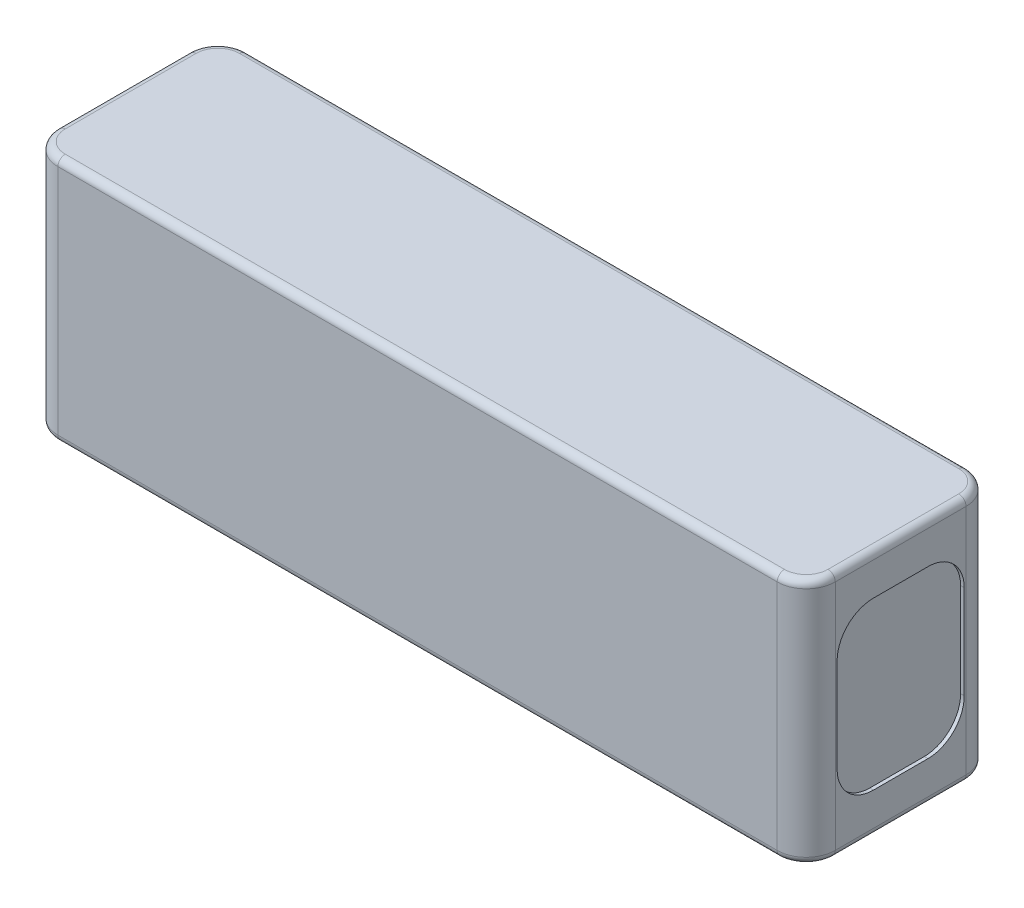
SolidWorks part; units mm, degrees
ref_plane "Front Plane" through (0, 0, 0) normal (0, 0, 1) x (1, 0, 0)
ref_plane "Top Plane" through (0, 0, 0) normal (0, 1, 0) x (1, 0, 0)
ref_plane "Right Plane" through (0, 0, 0) normal (1, 0, 0) x (0, 0, -1)
ref_plane "Plane1" through (0, 0, -15) normal (0, 0, -1) x (-1, 0, 0)
sketch "Sketch1" plane through (0, 0, -15) normal (0, 0, -1) x (-1, 0, 0)
  line L0 (-69, -22) -> (38, -22)
  line L1 (38, -22) -> (38, 12)
  line L2 (38, 12) -> (-69, 12)
  line L3 (-69, 12) -> (-69, -22)
  line L4 (-69, -5) -> (38, -5) construction
  line L5 (-15.5, 12) -> (-15.5, -22) construction
  dimension "D1" = 34
  dimension "D2" = 107
extrude "Boss-Extrude1" add sketch "Sketch1" against normal blind 26
sketch "Sketch2" plane through (69, 0, 0) normal (1, 0, 0) x (0, 0, -1)
  line L0 (-6.75, 1.4423) -> (-6.75, -11.4423)
  line L1 (-1.75, -16.4423) -> (5.75, -16.4423)
  line L2 (10.75, -11.4423) -> (10.75, 1.4423)
  line L3 (5.75, 6.4423) -> (-1.75, 6.4423)
  line L4 (-11, 12) -> (15, -22) construction
  line L5 (15, 12) -> (-11, -22) construction
  line L6 (-6.75, 6.4423) -> (10.75, -16.4423) construction
  line L7 (10.75, 6.4423) -> (-6.75, -16.4423) construction
  line L12 (-11, 12) -> (15, 12) construction
  line L13 (-11, 12) -> (-11, -22) construction
  line L14 (-11, -22) -> (15, -22) construction
  line L15 (15, 12) -> (15, -22) construction
  line L16 (-11, 12) -> (15, -22) construction
  line L17 (-11, -22) -> (15, 12) construction
  arc A0 (-6.75, -11.4423) -> (-1.75, -16.4423) centre (-1.75, -11.4423) ccw
  arc A1 (5.75, -16.4423) -> (10.75, -11.4423) centre (5.75, -11.4423) ccw
  arc A2 (10.75, 1.4423) -> (5.75, 6.4423) centre (5.75, 1.4423) ccw
  arc A3 (-6.75, 1.4423) -> (-1.75, 6.4423) centre (-1.75, 1.4423) cw
  point P16 (2, -5)
  dimension "D2" = 26
  dimension "D3" = 5
  dimension "D1" = 17.5
extrude "Cut-Extrude1" cut sketch "Sketch2" against normal blind 0.5
sketch "Sketch3" plane through (-38, 0, 0) normal (-1, 0, 0) x (0, 0, 1)
  line L0 (-0.625, 7.2596) -> (-3.375, 7.2596)
  line L1 (-11.375, -0.7404) -> (-11.375, -9.2596)
  line L2 (-3.375, -17.2596) -> (-0.625, -17.2596)
  line L3 (7.375, -9.2596) -> (7.375, -0.7404)
  line L4 (-11.375, 7.2596) -> (7.375, -17.2596) construction
  line L5 (7.375, 7.2596) -> (-11.375, -17.2596) construction
  line L6 (-15, 12) -> (11, -22) construction
  line L7 (11, -22) -> (-15, -22) construction
  line L8 (-15, -22) -> (11, 12) construction
  arc A0 (-11.375, -9.2596) -> (-3.375, -17.2596) centre (-3.375, -9.2596) ccw
  arc A1 (-0.625, -17.2596) -> (7.375, -9.2596) centre (-0.625, -9.2596) ccw
  arc A2 (-0.625, 7.2596) -> (7.375, -0.7404) centre (-0.625, -0.7404) cw
  arc A3 (-3.375, 7.2596) -> (-11.375, -0.7404) centre (-3.375, -0.7404) ccw
  dimension "D3" = 8
  dimension "D1" = 18.75
  dimension "D2" = 26
extrude "Cut-Extrude2" cut sketch "Sketch3" against normal blind 0.5
fillet "Fillet1" radius 4 4 edges at (-38, -5, -15) (-38, -5, 11) (69, -5, -15) (69, -5, 11) tangent propagation no
fillet "Fillet2" radius 1 16 edges at (67.8284, 12, -13.8284) (69, 12, -2) (15.5, 12, -15) (67.8284, 12, 9.8284) (-36.8284, 12, -13.8284) (15.5, 12, 11) (-38, 12, -2) (-36.8284, 12, 9.8284) (-38, -22, -2) (-36.8284, -22, -13.8284) (-36.8284, -22, 9.8284) (15.5, -22, -15) (15.5, -22, 11) (67.8284, -22, -13.8284) (67.8284, -22, 9.8284) (69, -22, -2) tangent propagation no
sketch "Sketch4" [suppressed] plane through (0, 0, 10) normal (0, 0, 1) x (1, 0, 0)
  line L0 (-75, 4) -> (65, 4) construction
  line L1 (-75, 29) -> (-75, -21) construction
  line L2 (65, -21) -> (65, 29) construction
  line L3 (-5, 25.9735) -> (-5, -21) construction
  line L4 (-75, -21) -> (65, -21) construction
  circle A0 centre (-5, 4) radius 0.5026
sketch "Sketch5" plane through (68.5, 0, 0) normal (1, 0, 0) x (0, 0, -1)
  line L0 (7, 8) -> (-3, 8) construction
  line L1 (2, 12) -> (2, 8) construction
  line L2 (-7, 12) -> (11, 12) construction
  circle A0 centre (-3, 8) radius 2
  circle A1 centre (7, 8) radius 2
  dimension "D1" = 4
  dimension "D2" = 10
  dimension "D3" = 4
equation "\"D1@Sketch3\"=\"D2@Sketch3\" * .75"
equation "\"D1@Sketch2\"=\"D2@Sketch2\"* .7"
